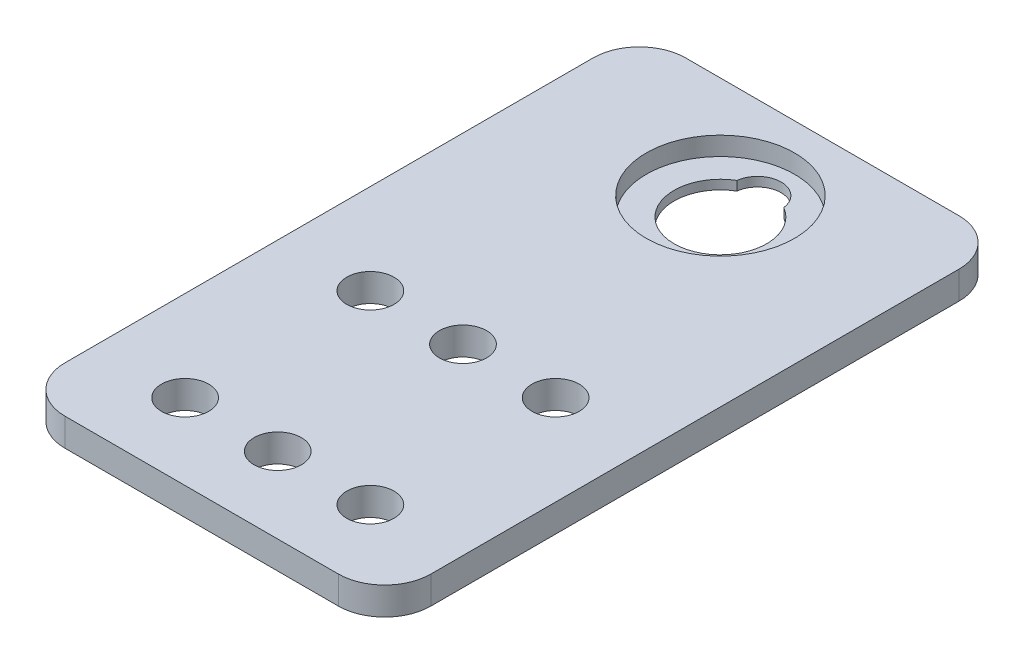
SolidWorks part; units mm, degrees
material "6061-T6 (SS)"
ref_plane "Front Plane" through (0, 0, 0) normal (0, 0, 1) x (1, 0, 0)
ref_plane "Top Plane" through (0, 0, 0) normal (0, 1, 0) x (1, 0, 0)
ref_plane "Right Plane" through (0, 0, 0) normal (1, 0, 0) x (0, 0, -1)
sketch "Sketch1" plane through (0, 0, 0) normal (0, 1, 0) x (1, 0, 0)
  line L0 (-19.75, 0) -> (0, 0) construction
  line L1 (14.75, -33.5) -> (-14.75, -33.5)
  line L2 (19.75, -28.5) -> (19.75, 28.5)
  line L3 (14.75, 33.5) -> (-14.75, 33.5)
  line L4 (-19.75, -28.5) -> (-19.75, 28.5)
  line L5 (0, 33.5) -> (0, 0) construction
  line L9 (10, -25.29) -> (0, -25.29) construction
  arc A0 (-14.75, -33.5) -> (-19.75, -28.5) centre (-14.75, -28.5) cw
  arc A1 (14.75, -33.5) -> (19.75, -28.5) centre (14.75, -28.5) ccw
  arc A2 (19.75, 28.5) -> (14.75, 33.5) centre (14.75, 28.5) ccw
  arc A3 (-14.75, 33.5) -> (-19.75, 28.5) centre (-14.75, 28.5) ccw
  circle A4 centre (0, 26.5) radius 2.55
  circle A7 centre (10, -25.29) radius 2.55
  circle A8 centre (10, -5.29) radius 2.55
  circle A9 centre (0, -25.29) radius 2.55
  circle A10 centre (0, -5.29) radius 2.55
  circle A11 centre (-10, -25.29) radius 2.55
  circle A12 centre (-10, -5.29) radius 2.55
  dimension "D2" = 5
  dimension "D3" = 7
  dimension "D7" = 20
  dimension "D10" = 3
  dimension "D8" = 9.75
  dimension "D6" = 5.1
  dimension "D1" = 67
  dimension "D9" = 39.5
  dimension "D11" = 10
  dimension "D12" = 8.21
extrude "Boss-Extrude1" add sketch "Sketch1" along normal blind 3
sketch "Sketch5" plane through (0, 3, 0) normal (0, 1, 0) x (1, 0, 0)
  circle A0 centre (0, 22.5) radius 8.002
  circle A1 centre (0, 26.5) radius 2.55 construction
  dimension "D2" = 4
  dimension "D1" = 0
extrude "Cut-Extrude8" cut sketch "Sketch5" against normal blind 2
sketch "Sketch6" plane through (0, 3, 0) normal (0, 1, 0) x (1, 0, 0)
  circle A0 centre (0, 22.5) radius 5
extrude "Cut-Extrude9" cut sketch "Sketch6" against normal blind 10
